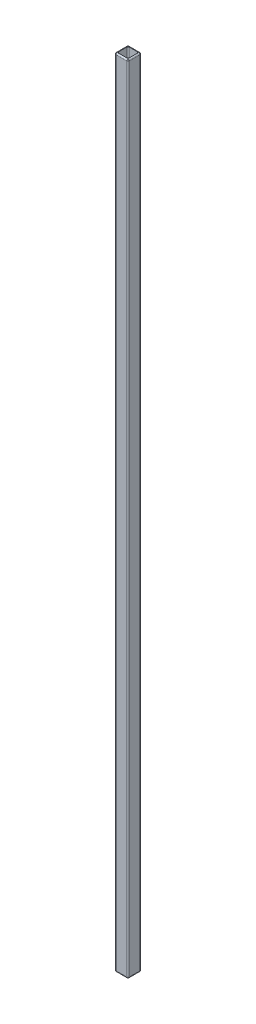
SolidWorks part; units mm, degrees
ref_plane "Front Plane" through (0, 0, 0) normal (0, 0, 1) x (1, 0, 0)
ref_plane "Top Plane" through (0, 0, 0) normal (0, 1, 0) x (1, 0, 0)
ref_plane "Right Plane" through (0, 0, 0) normal (1, 0, 0) x (0, 0, -1)
sketch "Sketch4" plane through (0, 0, 0) normal (0, 1, 0) x (1, 0, 0)
  line L0 (10.16, 10.16) -> (10.16, -10.16)
  line L1 (12.7, 12.7) -> (-12.7, 12.7)
  line L2 (12.7, 12.7) -> (12.7, -12.7)
  line L3 (12.7, -12.7) -> (-12.7, -12.7)
  line L4 (-12.7, 12.7) -> (-12.7, -12.7)
  line L5 (10.16, -10.16) -> (-10.16, -10.16)
  line L6 (-10.16, 10.16) -> (-10.16, -10.16)
  line L7 (10.16, 10.16) -> (-10.16, 10.16)
  point P0 (0, 0)
  dimension "D1" = 25.4
  dimension "D2" = 25.4
  dimension "D3" = 2.54
extrude "Boss-Extrude6" add sketch "Sketch4" along normal blind 1524 contours L4 L3 L2 L1
shell "Shell1" thickness 2.54 removed face at (0, 0, 0) removed face at (0, 1524, 0)
fillet "Fillet1" radius 2.54 4 edges at (-12.7, 762, 12.7) (12.7, 762, 12.7) (12.7, 762, -12.7) (-12.7, 762, -12.7)
fillet "Fillet2" radius 2.54 1 edges at (-10.16, 762, -10.16)
fillet "Fillet3" radius 2.54 3 edges at (10.16, 762, -10.16) (-10.16, 762, 10.16) (10.16, 762, 10.16)
fillet "Fillet5" radius 2.54 8 edges at (11.9561, 1524, -11.9561) (-11.9561, 1524, -11.9561) (-11.9561, 1524, 11.9561) (11.9561, 1524, 11.9561) (0, 1524, 12.7) (-12.7, 1524, 0) (0, 1524, -12.7) (12.7, 1524, 0)
fillet "Fillet6" radius 2.54 8 edges at (11.9561, 0, -11.9561) (11.9561, 0, 11.9561) (-11.9561, 0, 11.9561) (-11.9561, 0, -11.9561) (0, 0, 12.7) (-12.7, 0, 0) (12.7, 0, 0) (0, 0, -12.7)
